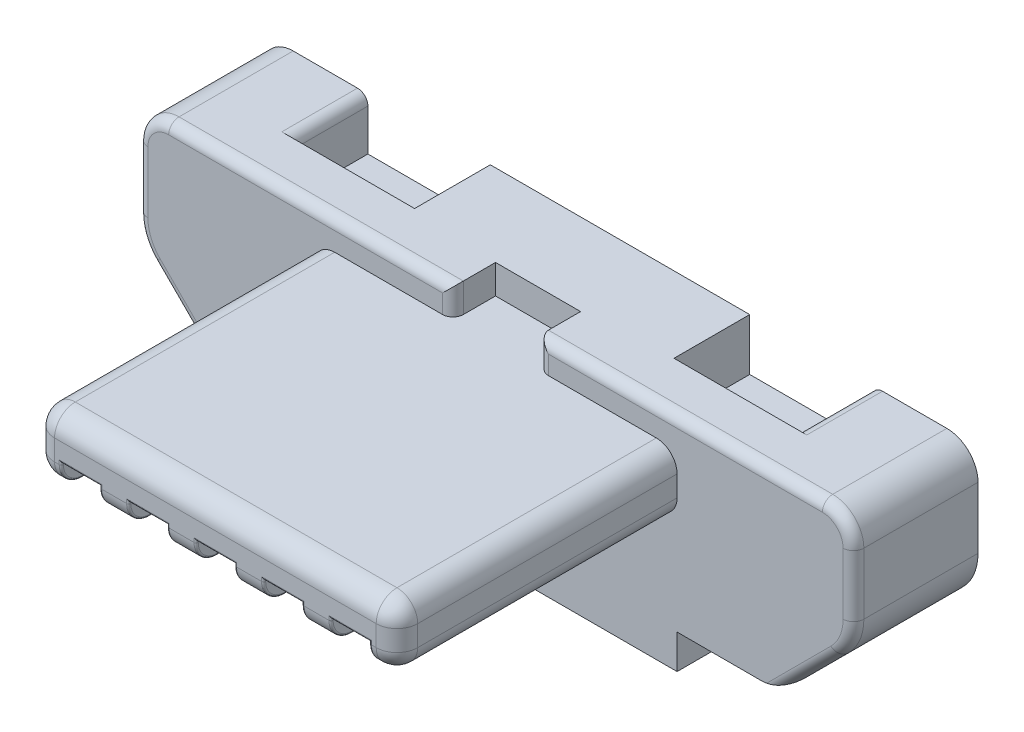
SolidWorks part; units mm, degrees
ref_plane "Front Plane" through (0, 0, 0) normal (0, 0, 1) x (1, 0, 0)
ref_plane "Top Plane" through (0, 0, 0) normal (0, 1, 0) x (1, 0, 0)
ref_plane "Right Plane" through (0, 0, 0) normal (1, 0, 0) x (0, 0, -1)
sketch "Sketch1" plane through (0, 0, 0) normal (0, 0, 1) x (1, 0, 0)
  line L0 (3.45, 0.925) -> (-3.45, 0.925)
  line L1 (-3.45, 0.925) -> (-3.45, -0.175)
  line L2 (-3.45, -0.175) -> (-2.7, -0.925)
  line L3 (-2.7, -0.925) -> (2.7, -0.925)
  line L4 (2.7, -0.925) -> (3.45, -0.175)
  line L5 (3.45, -0.175) -> (3.45, 0.925)
  line L6 (0, 0.925) -> (0, -0.925) construction
  dimension "D1" = 6.9
  dimension "D2" = 1.85
extrude "Boss-Extrude1" add sketch "Sketch1" along normal blind 1.2
fillet "Fillet1" radius 0.3 2 edges at (-3.45, 0.925, 0.6) (3.45, 0.925, 0.6)
sketch "Sketch4" plane through (0, 0.925, 0) normal (0, 1, 0) x (1, 0, 0)
  line L0 (-1.25, -0.73) -> (-2.43, -0.73)
  line L1 (-1.25, -0.73) -> (-1.25, 1.3361)
  line L2 (-1.25, 1.3361) -> (-2.43, 1.3361)
  line L3 (-2.43, -0.73) -> (-2.43, 1.3361)
  line L4 (2.43, -0.73) -> (1.25, -0.73)
  line L5 (2.43, -0.73) -> (2.43, 1.3361)
  line L6 (2.43, 1.3361) -> (1.25, 1.3361)
  line L7 (1.25, -0.73) -> (1.25, 1.3361)
  line L8 (-1.25, -0.73) -> (1.25, -0.73) construction
  line L9 (0, -0.73) -> (0, 1.3361) construction
  line L10 (3.15, 0) -> (-3.15, 0) construction
  dimension "D1" = 0.73
  dimension "D2" = 2.5
  dimension "D3" = 1.18
  dimension "D4" = 1.18
extrude "Cut-Extrude2" cut sketch "Sketch4" against normal blind 0.5
sketch "Sketch5" plane through (0, -0.925, 0) normal (0, -1, 0) x (1, 0, 0)
  line L0 (-2.7, 1.2) -> (2.7, 1.2) construction
  line L1 (-1.75, 1.2) -> (1.75, 1.2)
  line L2 (-1.75, 1.2) -> (-1.75, 0.8)
  line L3 (-1.75, 0.8) -> (1.75, 0.8)
  line L4 (1.75, 1.2) -> (1.75, 0.8)
  line L5 (0, 0.8) -> (0, 0) construction
  dimension "D1" = 0.4
  dimension "D2" = 3.5
extrude "Boss-Extrude3" add sketch "Sketch5" along normal blind 0.28
sketch "Sketch7" plane through (-1.75, 0, 0) normal (-1, 0, 0) x (0, 0, 1)
  line L0 (0, -0.925) -> (1.2, -0.875)
  line L1 (1.2, -0.925) -> (0, -0.925)
  line L2 (1.2, -0.925) -> (1.2, -0.875)
  dimension "D1" = 0.05
extrude "Cut-Extrude3" cut sketch "Sketch7" along normal blind 2.28
sketch "Sketch8" plane through (1.75, 0, 0) normal (1, 0, 0) x (0, 0, -1)
  line L3 (0, -0.925) -> (-1.2, -0.875)
  line L4 (-1.2, -0.875) -> (-1.2, -0.925)
  line L5 (-1.2, -0.925) -> (0, -0.925)
  line L6 (0, -0.925) -> (-1.2, -0.875)
  line L7 (-1.2, -0.875) -> (-1.2, -0.925)
  line L8 (-1.2, -0.925) -> (0, -0.925)
  dimension "D1" = 0
extrude "Cut-Extrude4" cut sketch "Sketch8" along normal blind 2.28
sketch "Sketch2" plane through (0, 0, 1.2) normal (0, 0, 1) x (1, 0, 0)
  line L1 (-0.41, 1.465) -> (0.41, 1.465)
  line L2 (-0.41, 1.465) -> (-0.41, 0.645)
  line L3 (-0.41, 0.645) -> (0.41, 0.645)
  line L4 (0.41, 1.465) -> (0.41, 0.645)
  line L5 (-0.41, 1.465) -> (0.41, 0.645) construction
  line L6 (-0.41, 0.645) -> (0.41, 1.465) construction
  line L7 (3.15, 0.925) -> (-3.15, 0.925) construction
  point P0 (0, 1.055)
  dimension "D1" = 0.82
  dimension "D2" = 0.28
extrude "Cut-Extrude1" cut sketch "Sketch2" against normal blind 0.41
sketch "Sketch3" plane through (0, 0, 1.2) normal (0, 0, 1) x (1, 0, 0)
  line L1 (-1.75, 0.645) -> (1.75, 0.645)
  line L2 (-1.75, 0.645) -> (-1.75, 0.045)
  line L3 (-1.75, 0.045) -> (1.75, 0.045)
  line L4 (1.75, 0.645) -> (1.75, 0.045)
  line L5 (-1.75, 0.645) -> (1.75, 0.045) construction
  line L6 (-1.75, 0.045) -> (1.75, 0.645) construction
  line L7 (3.15, 0.925) -> (0.41, 0.925) construction
  point P0 (0, 0.345)
  dimension "D1" = 0.28
  dimension "D2" = 3.5
  dimension "D3" = 0.6
extrude "Boss-Extrude2" add sketch "Sketch3" along normal blind 2.7
fillet "Fillet5" radius 0.2 8 edges at (0, 0.045, 3.9) (-1.75, 0.345, 3.9) (0, 0.645, 3.9) (1.75, 0.345, 3.9) (-1.75, 0.045, 2.55) (-1.75, 0.645, 2.55) (1.75, 0.045, 2.55) (1.75, 0.645, 2.55)
fillet "Fillet7" radius 0.5 4 edges at (3.45, -0.175, 0.6) (2.725, -0.9, 0.6) (-2.725, -0.9, 0.6) (-3.45, -0.175, 0.6)
fillet "Fillet8" radius 0.1 12 edges at (-3.45, 0.3286, 1.2) (3.45, 0.3286, 1.2) (3.3621, 0.8371, 1.2) (-3.3621, 0.8371, 1.2) (-1.78, 0.925, 1.2) (1.78, 0.925, 1.2) (3.1002, -0.5248, 1.2) (-3.1002, -0.5248, 1.2) (3.4119, -0.1592, 1.2) (-3.4119, -0.1592, 1.2)
fillet "Fillet9" radius 0.1 2 edges at (2.43, 0.925, 0.365) (-2.43, 0.925, 0.365)
sketch "Sketch9" plane through (0, -0.925, 0) normal (0, -1, 0) x (1, 0, 0)
  line L0 (1.75, 0.8) -> (1.75, 0) construction
  line L1 (-1.75, 0.05) -> (1.75, 0.05)
  line L2 (-1.75, 0.05) -> (-1.75, 0.65)
  line L3 (-1.75, 0.65) -> (1.75, 0.65)
  line L4 (1.75, 0.05) -> (1.75, 0.65)
  line L5 (-1.75, 0) -> (1.75, 0) construction
  dimension "D1" = 0.05
  dimension "D2" = 0.6
extrude "Boss-Extrude4" add sketch "Sketch9" along normal blind 0.16
sketch "Sketch10" plane through (0, 0, 3.9) normal (0, 0, 1) x (1, 0, 0)
  line L0 (-1.3, 0.265) -> (-1.3, -0.105) construction
  line L1 (-1.485, 0.265) -> (-1.115, 0.265)
  line L2 (-1.485, 0.265) -> (-1.485, -0.105)
  line L3 (-1.485, -0.105) -> (-1.115, -0.105)
  line L4 (-1.115, 0.265) -> (-1.115, -0.105)
  line L5 (-0.835, 0.265) -> (-0.465, 0.265)
  line L6 (-0.835, 0.265) -> (-0.835, -0.105)
  line L7 (-0.835, -0.105) -> (-0.465, -0.105)
  line L8 (-0.465, 0.265) -> (-0.465, -0.105)
  line L9 (-0.185, 0.265) -> (0.185, 0.265)
  line L10 (-0.185, 0.265) -> (-0.185, -0.105)
  line L11 (-0.185, -0.105) -> (0.185, -0.105)
  line L12 (0.185, 0.265) -> (0.185, -0.105)
  line L13 (0.465, 0.265) -> (0.835, 0.265)
  line L14 (0.465, 0.265) -> (0.465, -0.105)
  line L15 (0.465, -0.105) -> (0.835, -0.105)
  line L16 (0.835, 0.265) -> (0.835, -0.105)
  line L17 (1.115, 0.265) -> (1.485, 0.265)
  line L18 (1.115, 0.265) -> (1.115, -0.105)
  line L19 (1.115, -0.105) -> (1.485, -0.105)
  line L20 (1.485, 0.265) -> (1.485, -0.105)
  line L21 (1.3, 0.265) -> (1.3, -0.105) construction
  line L22 (0.65, 0.265) -> (0.65, -0.105) construction
  line L23 (0, 0.265) -> (0, -0.105) construction
  line L24 (-0.65, 0.265) -> (-0.65, -0.105) construction
  line L25 (-1.55, 0.045) -> (1.55, 0.045) construction
  dimension "D1" = 0.37
  dimension "D2" = 2.6
  dimension "D3" = 0.28
  dimension "D4" = 0.28
  dimension "D5" = 0.28
  dimension "D6" = 0.28
  dimension "D7" = 0.22
extrude "Cut-Extrude5" cut sketch "Sketch10" against normal up to surface (2.7 mm away) up to face at (0.0371, 0.0086, 1.2)
ref_plane "Plane1" through (0, 0, 3.7) normal (0, 0, 1) x (1, 0, 0)
sketch "Sketch11" plane through (0, 0, 3.7) normal (0, 0, 1) x (1, 0, 0)
  line L0 (-1.485, 0.045) -> (-1.485, 0.265) construction
  line L1 (-1.485, 0.165) -> (-1.115, 0.165)
  line L2 (-1.485, 0.165) -> (-1.485, 0.315)
  line L3 (-1.485, 0.315) -> (-1.115, 0.315)
  line L4 (-1.115, 0.165) -> (-1.115, 0.315)
  line L5 (-0.51, 0.645) -> (-1.55, 0.645) construction
  line L6 (-1.115, 0.245) -> (-1.115, 0.045) construction
  line L7 (-0.835, 0.315) -> (-0.465, 0.315)
  line L8 (-0.835, 0.165) -> (-0.835, 0.315)
  line L9 (-0.835, 0.165) -> (-0.465, 0.165)
  line L10 (-0.465, 0.165) -> (-0.465, 0.315)
  line L11 (-0.185, 0.315) -> (0.185, 0.315)
  line L12 (-0.185, 0.165) -> (-0.185, 0.315)
  line L13 (-0.185, 0.165) -> (0.185, 0.165)
  line L14 (0.185, 0.165) -> (0.185, 0.315)
  line L15 (0.465, 0.315) -> (0.835, 0.315)
  line L16 (0.465, 0.165) -> (0.465, 0.315)
  line L17 (0.465, 0.165) -> (0.835, 0.165)
  line L18 (0.835, 0.165) -> (0.835, 0.315)
  line L19 (1.115, 0.315) -> (1.485, 0.315)
  line L20 (1.115, 0.165) -> (1.115, 0.315)
  line L21 (1.115, 0.165) -> (1.485, 0.165)
  line L22 (1.485, 0.165) -> (1.485, 0.315)
  dimension "D1" = 0.15
  dimension "D2" = 0.48
  dimension "D3" = 5
sketch "Sketch12" plane through (0, 0, 0) normal (1, 0, 0) x (0, 0, -1)
  line L0 (-3.7, 0.315) -> (-0.55, 0.315)
  line L1 (-3.7, 0.165) -> (-3.7, 0.315) construction
  line L2 (-3.7, 0.165) -> (-3.7, 0.315) construction
  line L3 (-0.35, 0.115) -> (-0.35, -1.085)
  line L4 (0, -0.7781) -> (0, -0.3214) construction
  line L5 (-0.05, -1.085) -> (-0.65, -1.085) construction
  arc A0 (-0.55, 0.315) -> (-0.35, 0.115) centre (-0.55, 0.115) cw
  dimension "D1" = 0.2
  dimension "D2" = 0.35
sketch "Sketch13" plane through (0, 0, 3.7) normal (0, 0, 1) x (1, 0, 0)
  line L0 (-1.485, 0.315) -> (-1.115, 0.315) construction
  line L1 (-1.425, 0.315) -> (-1.175, 0.315)
  line L2 (-1.425, 0.315) -> (-1.425, 0.165)
  line L3 (-1.425, 0.165) -> (-1.175, 0.165)
  line L4 (-1.175, 0.315) -> (-1.175, 0.165)
  line L5 (-1.485, 0.165) -> (-1.115, 0.165) construction
  line L6 (-1.485, 0.045) -> (-1.175, 0.315) construction
  line L7 (-1.175, 0.315) -> (-1.1728, 0.3168) construction
  line L8 (-1.115, 0.045) -> (-1.425, 0.315) construction
  line L12 (-0.775, 0.315) -> (-0.525, 0.315)
  line L13 (-0.775, 0.315) -> (-0.775, 0.165)
  line L14 (-0.775, 0.165) -> (-0.525, 0.165)
  line L15 (-0.525, 0.315) -> (-0.525, 0.165)
  line L16 (-0.125, 0.315) -> (0.125, 0.315)
  line L17 (-0.125, 0.315) -> (-0.125, 0.165)
  line L18 (-0.125, 0.165) -> (0.125, 0.165)
  line L19 (0.125, 0.315) -> (0.125, 0.165)
  line L20 (0.525, 0.315) -> (0.775, 0.315)
  line L21 (0.525, 0.315) -> (0.525, 0.165)
  line L22 (0.525, 0.165) -> (0.775, 0.165)
  line L23 (0.775, 0.315) -> (0.775, 0.165)
  line L24 (1.175, 0.315) -> (1.425, 0.315)
  line L25 (1.175, 0.315) -> (1.175, 0.165)
  line L26 (1.175, 0.165) -> (1.425, 0.165)
  line L27 (1.425, 0.315) -> (1.425, 0.165)
  dimension "D1" = 0.25
  dimension "D2" = 5
sweep "Cut-Sweep2" cut profiles "Sketch13" path "Sketch12"
extrude "Cut-Extrude6" cut sketch "Sketch11" against normal blind 2.8
sketch "Sketch14" plane through (0, 0, 3.7) normal (0, 0, 1) x (1, 0, 0)
  line L4 (-1.175, 0.315) -> (-1.425, 0.315)
  line L5 (-1.175, 0.165) -> (-1.175, 0.315)
  line L6 (-1.425, 0.165) -> (-1.175, 0.165)
  line L7 (-1.425, 0.315) -> (-1.425, 0.165)
  line L8 (-1.175, 0.315) -> (-1.425, 0.315)
  line L9 (-1.175, 0.165) -> (-1.175, 0.315)
  line L10 (-1.425, 0.165) -> (-1.175, 0.165)
  line L11 (-1.425, 0.315) -> (-1.425, 0.165)
  line L12 (1.425, 0.315) -> (1.175, 0.315)
  line L13 (1.425, 0.165) -> (1.425, 0.315)
  line L14 (1.175, 0.165) -> (1.425, 0.165)
  line L15 (1.175, 0.315) -> (1.175, 0.165)
  line L16 (1.425, 0.315) -> (1.175, 0.315)
  line L17 (1.425, 0.165) -> (1.425, 0.315)
  line L18 (1.175, 0.165) -> (1.425, 0.165)
  line L19 (1.175, 0.315) -> (1.175, 0.165)
  line L20 (0.775, 0.315) -> (0.525, 0.315)
  line L21 (0.775, 0.165) -> (0.775, 0.315)
  line L22 (0.525, 0.165) -> (0.775, 0.165)
  line L23 (0.525, 0.315) -> (0.525, 0.165)
  line L24 (0.775, 0.315) -> (0.525, 0.315)
  line L25 (0.775, 0.165) -> (0.775, 0.315)
  line L26 (0.525, 0.165) -> (0.775, 0.165)
  line L27 (0.525, 0.315) -> (0.525, 0.165)
  line L28 (0.125, 0.315) -> (-0.125, 0.315)
  line L29 (0.125, 0.165) -> (0.125, 0.315)
  line L30 (-0.125, 0.165) -> (0.125, 0.165)
  line L31 (-0.125, 0.315) -> (-0.125, 0.165)
  line L32 (0.125, 0.315) -> (-0.125, 0.315)
  line L33 (0.125, 0.165) -> (0.125, 0.315)
  line L34 (-0.125, 0.165) -> (0.125, 0.165)
  line L35 (-0.125, 0.315) -> (-0.125, 0.165)
  line L36 (-0.525, 0.315) -> (-0.775, 0.315)
  line L37 (-0.775, 0.315) -> (-0.775, 0.165)
  line L38 (-0.775, 0.165) -> (-0.525, 0.165)
  line L39 (-0.525, 0.165) -> (-0.525, 0.315)
  line L40 (-0.525, 0.315) -> (-0.775, 0.315)
  line L41 (-0.775, 0.315) -> (-0.775, 0.165)
  line L42 (-0.775, 0.165) -> (-0.525, 0.165)
  line L43 (-0.525, 0.165) -> (-0.525, 0.315)
  dimension "D1" = 0
  dimension "D2" = 0
  dimension "D3" = 0
  dimension "D4" = 0
  dimension "D5" = 0
sketch "Sketch15" plane through (0, 0, 0) normal (1, 0, 0) x (0, 0, -1)
  line L1 (0, -0.7781) -> (0, -0.3214) construction
  line L4 (-0.35, 0.115) -> (-0.35, -1.085) construction
  line L5 (-3.7, 0.315) -> (-0.55, 0.315) construction
  line L6 (-0.35, 0.115) -> (-0.35, -1.035)
  line L7 (-0.3, -1.085) -> (0.3, -1.085)
  line L9 (-0.05, -1.085) -> (-0.65, -1.085) construction
  line L10 (-3.7, 0.315) -> (-0.55, 0.315)
  arc A2 (-0.35, 0.115) -> (-0.55, 0.315) centre (-0.55, 0.115) ccw construction
  arc A4 (-0.35, -1.035) -> (-0.3, -1.085) centre (-0.3, -1.035) ccw
  arc A5 (-0.35, 0.115) -> (-0.55, 0.315) centre (-0.55, 0.115) ccw
  dimension "D1" = 0.3
  dimension "D2" = 0.05
sweep "Sweep3" add profiles "Sketch14" path "Sketch15"
sketch "Sketch16" plane through (0, -1.085, 0) normal (0, -1, 0) x (1, 0, 0)
  line L0 (1.75, 0.65) -> (-1.75, 0.65) construction
  line L1 (-1.175, 0.5) -> (-1.425, 0.5)
  line L2 (-1.175, 0.5) -> (-1.175, 0.65)
  line L3 (-1.175, 0.65) -> (-1.425, 0.65)
  line L4 (-1.425, 0.5) -> (-1.425, 0.65)
  line L5 (-1.425, 0.5) -> (-1.425, 0.3) construction
  line L6 (-0.775, 0.5) -> (-0.775, 0.65)
  line L7 (-0.525, 0.65) -> (-0.775, 0.65)
  line L8 (-0.525, 0.5) -> (-0.525, 0.65)
  line L9 (-0.525, 0.5) -> (-0.775, 0.5)
  line L10 (-0.125, 0.5) -> (-0.125, 0.65)
  line L11 (0.125, 0.65) -> (-0.125, 0.65)
  line L12 (0.125, 0.5) -> (0.125, 0.65)
  line L13 (0.125, 0.5) -> (-0.125, 0.5)
  line L14 (0.525, 0.5) -> (0.525, 0.65)
  line L15 (0.775, 0.65) -> (0.525, 0.65)
  line L16 (0.775, 0.5) -> (0.775, 0.65)
  line L17 (0.775, 0.5) -> (0.525, 0.5)
  line L18 (1.175, 0.5) -> (1.175, 0.65)
  line L19 (1.425, 0.65) -> (1.175, 0.65)
  line L20 (1.425, 0.5) -> (1.425, 0.65)
  line L21 (1.425, 0.5) -> (1.175, 0.5)
  dimension "D1" = 5
extrude "Cut-Extrude7" cut sketch "Sketch16" against normal up to surface (0.16 mm away) up to face at (0, -0.925, 0.725)
sketch "Sketch17" plane through (0, 0, 3.7) normal (0, 0, 1) x (1, 0, 0)
  line L4 (-0.465, 0.315) -> (-0.835, 0.315)
  line L5 (-0.465, 0.165) -> (-0.465, 0.315)
  line L6 (-0.835, 0.165) -> (-0.465, 0.165)
  line L7 (-0.835, 0.315) -> (-0.835, 0.165)
  line L8 (-0.465, 0.315) -> (-0.835, 0.315)
  line L9 (-0.465, 0.165) -> (-0.465, 0.315)
  line L10 (-0.835, 0.165) -> (-0.465, 0.165)
  line L11 (-0.835, 0.315) -> (-0.835, 0.165)
  line L12 (-1.485, 0.165) -> (-1.115, 0.165)
  line L13 (-1.115, 0.165) -> (-1.115, 0.315)
  line L14 (-1.115, 0.315) -> (-1.485, 0.315)
  line L15 (-1.485, 0.315) -> (-1.485, 0.165)
  line L16 (-1.485, 0.165) -> (-1.115, 0.165)
  line L17 (-1.115, 0.165) -> (-1.115, 0.315)
  line L18 (-1.115, 0.315) -> (-1.485, 0.315)
  line L19 (-1.485, 0.315) -> (-1.485, 0.165)
  line L20 (1.485, 0.315) -> (1.115, 0.315)
  line L21 (1.485, 0.165) -> (1.485, 0.315)
  line L22 (1.115, 0.165) -> (1.485, 0.165)
  line L23 (1.115, 0.315) -> (1.115, 0.165)
  line L24 (1.485, 0.315) -> (1.115, 0.315)
  line L25 (1.485, 0.165) -> (1.485, 0.315)
  line L26 (1.115, 0.165) -> (1.485, 0.165)
  line L27 (1.115, 0.315) -> (1.115, 0.165)
  line L28 (0.835, 0.315) -> (0.465, 0.315)
  line L29 (0.835, 0.165) -> (0.835, 0.315)
  line L30 (0.465, 0.165) -> (0.835, 0.165)
  line L31 (0.465, 0.315) -> (0.465, 0.165)
  line L32 (0.835, 0.315) -> (0.465, 0.315)
  line L33 (0.835, 0.165) -> (0.835, 0.315)
  line L34 (0.465, 0.165) -> (0.835, 0.165)
  line L35 (0.465, 0.315) -> (0.465, 0.165)
  line L36 (0.185, 0.315) -> (-0.185, 0.315)
  line L37 (0.185, 0.165) -> (0.185, 0.315)
  line L38 (-0.185, 0.165) -> (0.185, 0.165)
  line L39 (-0.185, 0.315) -> (-0.185, 0.165)
  line L40 (0.185, 0.315) -> (-0.185, 0.315)
  line L41 (0.185, 0.165) -> (0.185, 0.315)
  line L42 (-0.185, 0.165) -> (0.185, 0.165)
  line L43 (-0.185, 0.315) -> (-0.185, 0.165)
  dimension "D1" = 0
  dimension "D2" = 0
  dimension "D3" = 0
  dimension "D4" = 0
  dimension "D5" = 0
extrude "Boss-Extrude5" add sketch "Sketch17" against normal blind 2.8
sketch "Sketch18" plane through (0, 0.315, 0) normal (0, -1, 0) x (1, 0, 0)
  line L0 (0.11, 3.7) -> (-0.11, 3.7) construction
  line L1 (1.115, 3.7) -> (1.485, 3.7)
  line L2 (1.115, 3.7) -> (1.115, 3.55)
  line L3 (1.115, 3.55) -> (1.485, 3.55)
  line L4 (1.485, 3.7) -> (1.485, 3.55)
  line L5 (1.115, 1.2) -> (1.115, 3.7) construction
  line L6 (1.485, 3.7) -> (1.485, 1.2) construction
  line L7 (0.465, 3.7) -> (0.835, 3.7)
  line L8 (0.465, 3.55) -> (0.835, 3.55)
  line L9 (0.465, 3.7) -> (0.465, 3.55)
  line L10 (0.835, 3.7) -> (0.835, 3.55)
  line L11 (-0.185, 3.7) -> (0.185, 3.7)
  line L12 (-0.185, 3.55) -> (0.185, 3.55)
  line L13 (-0.185, 3.7) -> (-0.185, 3.55)
  line L14 (0.185, 3.7) -> (0.185, 3.55)
  line L15 (-0.835, 3.7) -> (-0.465, 3.7)
  line L16 (-0.835, 3.55) -> (-0.465, 3.55)
  line L17 (-0.835, 3.7) -> (-0.835, 3.55)
  line L18 (-0.465, 3.7) -> (-0.465, 3.55)
  line L19 (-1.485, 3.7) -> (-1.115, 3.7)
  line L20 (-1.485, 3.55) -> (-1.115, 3.55)
  line L21 (-1.485, 3.7) -> (-1.485, 3.55)
  line L22 (-1.115, 3.7) -> (-1.115, 3.55)
  line L23 (-1.485, 0.9) -> (-1.485, 3.7) construction
  dimension "D1" = 0.15
  dimension "D2" = 5
extrude "Cut-Extrude8" cut sketch "Sketch18" against normal blind 0.15
fillet "Fillet10" radius 0.1 10 edges at (1.3, 0.315, 3.55) (0.65, 0.315, 3.55) (0, 0.315, 3.55) (-0.65, 0.315, 3.55) (-1.3, 0.315, 3.55) (-1.3, -1.085, 0.35) (-0.65, -1.085, 0.35) (0, -1.085, 0.35) (0.65, -1.085, 0.35) (1.3, -1.085, 0.35)
sketch "Sketch19" plane through (0, 0.315, 0) normal (0, 1, 0) x (1, 0, 0)
  line L0 (-0.11, -3.7) -> (0.11, -3.7) construction
  line L1 (-1.485, -3.7) -> (-1.115, -3.7)
  line L2 (-1.485, -3.7) -> (-1.485, -3.55)
  line L3 (-1.485, -3.55) -> (-1.115, -3.55)
  line L4 (-1.115, -3.7) -> (-1.115, -3.55)
  line L5 (-1.115, -0.9) -> (-1.115, -3.7) construction
  line L6 (-1.485, -0.9) -> (-1.485, -3.7) construction
  line L7 (-0.835, -3.7) -> (-0.835, -3.55)
  line L8 (-0.835, -3.55) -> (-0.465, -3.55)
  line L9 (-0.835, -3.7) -> (-0.465, -3.7)
  line L10 (-0.465, -3.7) -> (-0.465, -3.55)
  line L11 (-0.185, -3.7) -> (-0.185, -3.55)
  line L12 (-0.185, -3.55) -> (0.185, -3.55)
  line L13 (-0.185, -3.7) -> (0.185, -3.7)
  line L14 (0.185, -3.7) -> (0.185, -3.55)
  line L15 (0.465, -3.7) -> (0.465, -3.55)
  line L16 (0.465, -3.55) -> (0.835, -3.55)
  line L17 (0.465, -3.7) -> (0.835, -3.7)
  line L18 (0.835, -3.7) -> (0.835, -3.55)
  line L19 (1.115, -3.7) -> (1.115, -3.55)
  line L20 (1.115, -3.55) -> (1.485, -3.55)
  line L21 (1.115, -3.7) -> (1.485, -3.7)
  line L22 (1.485, -3.7) -> (1.485, -3.55)
  dimension "D1" = 0.15
extrude "Boss-Extrude6" add sketch "Sketch19" along normal blind 0.15
fillet "Fillet11" radius 0.15 1 edges at (1.3, 0.165, 3.7)
fillet "Fillet12" radius 0.15 1 edges at (0.65, 0.165, 3.7)
fillet "Fillet13" radius 0.15 1 edges at (0, 0.165, 3.7)
fillet "Fillet14" radius 0.15 1 edges at (-0.65, 0.165, 3.7)
fillet "Fillet15" radius 0.15 1 edges at (-1.3, 0.165, 3.7)
fillet "Fillet16" radius 0.01 11 edges at (-1.425, 0.1504, 0.5146) (-1.175, 0.1504, 0.5146) (-1.425, -0.46, 0.5) (-1.175, -0.46, 0.5) (-1.425, -1.1764, 0.4414) (-1.175, -1.1764, 0.4414) (-1.3, -1.235, -0.3) (-1.425, -1.235, 0) (-1.175, -1.235, 0) (-1.175, 0.165, 0.725) (-1.425, 0.165, 0.725)
fillet "Fillet17" radius 0.01 11 edges at (-0.775, 0.1504, 0.5146) (-0.525, 0.1504, 0.5146) (-0.775, -0.46, 0.5) (-0.525, -0.46, 0.5) (-0.775, -1.1764, 0.4414) (-0.525, -1.1764, 0.4414) (-0.65, -1.235, -0.3) (-0.775, -1.235, 0) (-0.525, -1.235, 0) (-0.525, 0.165, 0.725) (-0.775, 0.165, 0.725)
fillet "Fillet18" radius 0.01 11 edges at (-0.125, 0.1504, 0.5146) (0.125, 0.1504, 0.5146) (-0.125, -0.46, 0.5) (0.125, -0.46, 0.5) (-0.125, -1.1764, 0.4414) (0.125, -1.1764, 0.4414) (0, -1.235, -0.3) (-0.125, -1.235, 0) (0.125, -1.235, 0) (0.125, 0.165, 0.725) (-0.125, 0.165, 0.725)
fillet "Fillet19" radius 0.01 11 edges at (0.525, 0.1504, 0.5146) (0.775, 0.1504, 0.5146) (0.525, -0.46, 0.5) (0.775, -0.46, 0.5) (0.525, -1.1764, 0.4414) (0.775, -1.1764, 0.4414) (0.65, -1.235, -0.3) (0.525, -1.235, 0) (0.775, -1.235, 0) (0.775, 0.165, 0.725) (0.525, 0.165, 0.725)
fillet "Fillet20" radius 0.01 11 edges at (1.175, 0.1504, 0.5146) (1.425, 0.1504, 0.5146) (1.175, -0.46, 0.5) (1.425, -0.46, 0.5) (1.175, -1.1764, 0.4414) (1.425, -1.1764, 0.4414) (1.3, -1.235, -0.3) (1.175, -1.235, 0) (1.425, -1.235, 0) (1.425, 0.165, 0.725) (1.175, 0.165, 0.725)
fillet "Fillet21" radius 0.01 11 edges at (1.425, 0.315, 0.725) (1.175, 0.315, 0.725) (1.425, 0.2564, 0.4086) (1.175, 0.2564, 0.4086) (1.425, -0.46, 0.35) (1.175, -0.46, 0.35) (1.425, -1.0704, 0.3354) (1.175, -1.0704, 0.3354) (1.425, -1.085, 0) (1.175, -1.085, 0) (1.3, -1.085, -0.3)
fillet "Fillet22" radius 0.01 11 edges at (0.775, 0.315, 0.725) (0.525, 0.315, 0.725) (0.775, 0.2564, 0.4086) (0.525, 0.2564, 0.4086) (0.775, -0.46, 0.35) (0.525, -0.46, 0.35) (0.775, -1.0704, 0.3354) (0.525, -1.0704, 0.3354) (0.775, -1.085, 0) (0.525, -1.085, 0) (0.65, -1.085, -0.3)
fillet "Fillet23" radius 0.01 11 edges at (0.125, 0.315, 0.725) (-0.125, 0.315, 0.725) (0.125, 0.2564, 0.4086) (-0.125, 0.2564, 0.4086) (0.125, -0.46, 0.35) (-0.125, -0.46, 0.35) (0.125, -1.0704, 0.3354) (-0.125, -1.0704, 0.3354) (0.125, -1.085, 0) (-0.125, -1.085, 0) (0, -1.085, -0.3)
fillet "Fillet24" radius 0.01 11 edges at (-0.525, 0.315, 0.725) (-0.775, 0.315, 0.725) (-0.525, 0.2564, 0.4086) (-0.775, 0.2564, 0.4086) (-0.525, -0.46, 0.35) (-0.775, -0.46, 0.35) (-0.525, -1.0704, 0.3354) (-0.775, -1.0704, 0.3354) (-0.525, -1.085, 0) (-0.775, -1.085, 0) (-0.65, -1.085, -0.3)
fillet "Fillet25" radius 0.01 11 edges at (-1.175, 0.315, 0.725) (-1.425, 0.315, 0.725) (-1.175, 0.2564, 0.4086) (-1.425, 0.2564, 0.4086) (-1.175, -0.46, 0.35) (-1.425, -0.46, 0.35) (-1.175, -1.0704, 0.3354) (-1.425, -1.0704, 0.3354) (-1.175, -1.085, 0) (-1.425, -1.085, 0) (-1.3, -1.085, -0.3)
fillet "Fillet26" radius 0.02 35 edges at (1.115, 0.255, 3.9) (1.115, 0.045, 2.45) (-1.115, 0.045, 2.45) (-1.115, 0.255, 3.9) (-0.465, 0.045, 2.45) (-0.465, 0.255, 3.9) (0.185, 0.045, 2.45) (0.185, 0.255, 3.9) (0.835, 0.045, 2.45) (0.835, 0.255, 3.9) (1.485, 0.045, 2.45) (1.485, 0.255, 3.9) (-1.485, 0.255, 3.9) (-1.485, 0.045, 2.45) (-0.835, 0.255, 3.9) (-0.835, 0.045, 2.45) (-0.185, 0.255, 3.9) (-0.185, 0.045, 2.45) (0.465, 0.255, 3.9) (0.465, 0.045, 2.45) (1.115, 0.1036, 3.8414) (-1.115, 0.1036, 3.8414) (-0.465, 0.1036, 3.8414) (0.185, 0.1036, 3.8414) (0.835, 0.1036, 3.8414) (1.485, 0.1036, 3.8414) (-1.485, 0.1036, 3.8414) (-0.835, 0.1036, 3.8414) (-0.185, 0.1036, 3.8414) (0.465, 0.1036, 3.8414) (-1.3, 0.265, 3.9) (-0.65, 0.265, 3.9) (0, 0.265, 3.9) (0.65, 0.265, 3.9) (1.3, 0.265, 3.9)
